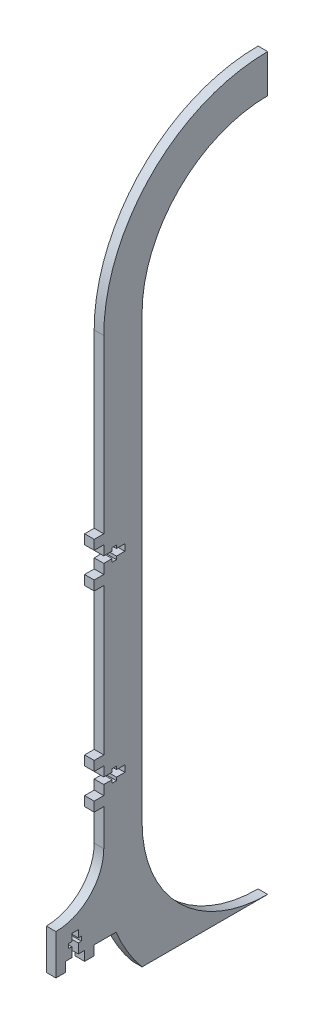
SolidWorks part; units mm, degrees
ref_plane "Front Plane" through (0, 0, 0) normal (0, 0, 1) x (1, 0, 0)
ref_plane "Top Plane" through (0, 0, 0) normal (0, 1, 0) x (1, 0, 0)
ref_plane "Right Plane" through (0, 0, 0) normal (1, 0, 0) x (0, 0, -1)
sketch "Elevator Ball Support Rail" plane through (0, 0, 0) normal (1, 0, 0) x (0, 0, -1)
  line L0 (83.312, 229.362) -> (83.312, 254.762)
  line L1 (-31.75, -124.587) -> (-25.4, -124.587)
  line L2 (83.312, -229.362) -> (0, -229.362)
  line L3 (-31.75, -200.787) -> (-17.2645, -200.787)
  line L4 (-38.1, -207.137) -> (-31.75, -207.137)
  line L5 (-38.1, -200.787) -> (-38.1, -207.137)
  line L6 (0, 146.05) -> (0, -146.05)
  line L7 (-25.4, -148.717) -> (-25.4, -200.787) construction
  line L8 (0, -146.05) -> (0, -229.362) construction
  line L9 (-31.75, -200.787) -> (-31.75, -207.137)
  line L10 (-50.8, -200.787) -> (-46.609, -200.787)
  line L11 (-25.4, 25.781) -> (-25.4, 19.431)
  line L12 (-57.15, -180.467) -> (-57.15, -207.137)
  line L13 (-57.15, -207.137) -> (-50.8, -207.137)
  line L14 (-42.291, -200.787) -> (-38.1, -200.787)
  line L15 (-50.8, -207.137) -> (-50.8, -200.787)
  line L16 (-42.291, -194.437) -> (-42.291, -200.787)
  line L17 (-42.291, -194.437) -> (-40.25, -194.437)
  line L18 (-40.25, -194.437) -> (-40.25, -191.537)
  line L19 (-42.291, -191.537) -> (-42.291, -186.817)
  line L20 (-42.291, -186.817) -> (-46.609, -186.817)
  line L21 (-40.25, -191.537) -> (-42.291, -191.537)
  line L22 (-48.65, -191.537) -> (-48.65, -194.437)
  line L23 (-48.65, -194.437) -> (-46.609, -194.437)
  line L24 (-46.609, -194.437) -> (-46.609, -200.787)
  line L25 (-46.609, -186.817) -> (-46.609, -191.537)
  line L26 (-46.609, -191.537) -> (-48.65, -191.537)
  line L27 (0, -200.787) -> (101.6, -200.787) construction
  line L28 (-31.75, 32.131) -> (-31.75, 25.781)
  line L29 (-31.75, 25.781) -> (-25.4, 25.781)
  line L30 (-25.4, 19.431) -> (-19.865, 19.431)
  line L31 (-19.865, 19.431) -> (-19.865, 21.472)
  line L32 (-19.865, 21.472) -> (-16.965, 21.472)
  line L33 (-16.965, 21.472) -> (-16.965, 19.431)
  line L34 (-16.965, 19.431) -> (-11.43, 19.431)
  line L35 (-11.43, 19.431) -> (-11.43, 15.113)
  line L36 (-11.43, 15.113) -> (-16.965, 15.113)
  line L37 (-16.965, 15.113) -> (-16.965, 13.072)
  line L38 (-16.965, 13.072) -> (-19.865, 13.072)
  line L39 (-19.865, 13.072) -> (-19.865, 15.113)
  line L40 (-19.865, 15.113) -> (-25.4, 15.113)
  line L41 (-25.4, 15.113) -> (-25.4, 8.763)
  line L42 (0, 0) -> (-25.4, 0) construction
  line L43 (-25.4, 8.763) -> (-31.75, 8.763)
  line L44 (-31.75, 8.763) -> (-31.75, 2.413)
  line L45 (-31.75, 2.413) -> (-25.4, 2.413)
  line L46 (-25.4, 2.413) -> (-25.4, -94.869)
  line L47 (-25.4, -94.869) -> (-31.75, -94.869)
  line L48 (-25.4, -101.219) -> (-25.4, -107.569)
  line L49 (-31.75, -94.869) -> (-31.75, -101.219)
  line L50 (-31.75, -101.219) -> (-25.4, -101.219)
  line L51 (-25.4, -107.569) -> (-19.865, -107.569)
  line L52 (-19.865, -107.569) -> (-19.865, -105.528)
  line L53 (-19.865, -105.528) -> (-16.965, -105.528)
  line L54 (-16.965, -105.528) -> (-16.965, -107.569)
  line L55 (-16.965, -107.569) -> (-11.43, -107.569)
  line L56 (-11.43, -107.569) -> (-11.43, -111.887)
  line L57 (-11.43, -111.887) -> (-16.965, -111.887)
  line L58 (-16.965, -111.887) -> (-16.965, -113.928)
  line L59 (-16.965, -113.928) -> (-19.865, -113.928)
  line L60 (-19.865, -113.928) -> (-19.865, -111.887)
  line L61 (-19.865, -111.887) -> (-25.4, -111.887)
  line L62 (-25.4, -111.887) -> (-25.4, -118.237)
  line L63 (-25.4, -118.237) -> (-31.75, -118.237)
  line L64 (-31.75, -118.237) -> (-31.75, -124.587)
  line L65 (-25.4, -148.717) -> (-25.4, -142.367)
  line L66 (-25.4, -124.587) -> (-25.4, -142.367)
  line L67 (-31.75, 32.131) -> (-25.4, 32.131)
  line L68 (-25.4, 32.131) -> (-25.4, 146.05)
  arc A0 (0, 146.05) -> (83.312, 229.362) centre (83.312, 146.05) cw
  arc A1 (83.312, 254.762) -> (-25.4, 146.05) centre (83.312, 146.05) ccw
  arc A2 (0, -146.05) -> (83.312, -229.362) centre (83.312, -146.05) ccw
  arc A3 (-17.2645, -200.787) -> (0, -229.362) centre (83.312, -159.5235) ccw
  arc A4 (-57.15, -180.467) -> (-25.4, -148.717) centre (-57.15, -148.717) ccw
  point P4 (0, 0)
  dimension "D5" = 25.4
  dimension "D4" = 83.312
  dimension "D7" = 83.312
  dimension "D8" = 6.35
  dimension "D14" = 12.7
  dimension "D13" = 6.35
  dimension "D6" = 6.35
  dimension "D3" = 292.1
  dimension "D9" = 22.225
  dimension "D10" = 6.35
  dimension "D11" = 6.35
  dimension "D12" = 6.35
  dimension "D15" = 2.9
  dimension "D16" = 8.4
  dimension "D17" = 6.35
  dimension "D18" = 4.318
  dimension "D19" = 13.97
  dimension "D20" = 54.737
  dimension "D21" = 6.35
  dimension "D22" = 6.35
  dimension "D23" = 4.318
  dimension "D24" = 2.9
  dimension "D25" = 8.4
  dimension "D26" = 6.35
  dimension "D27" = 13.97
  dimension "D28" = 6.35
  dimension "D29" = 4.318
  dimension "D30" = 2.9
  dimension "D31" = 13.97
  dimension "D32" = 6.35
  dimension "D33" = 8.4
  dimension "D34" = 6.35
  dimension "D35" = 6.35
  dimension "D36" = 25.4
  dimension "D37" = 76.2
  dimension "D38" = 203.2
extrude "Boss-Extrude2" add sketch "Elevator Ball Support Rail" along normal blind 6.35 contours A4 L12 L13 L15 L10 L24 L23 L22 L26 L25 L20 L19 L21 L18 L17 L16 L14 L5 L4 L9 L3 A3 L2 A2 L6 A0 L0 A1 L28 L29 L11 L30 L31 L32 L33 L34 L35 L36 L37 L38 L39 L40 L41 L43 L44 L45 L46 L47 L49 L50 region at (0, 1.1865, 2.4978)
equation "\"Ball Diameter\"= 1.75in"
equation "\"Pulley Diameter\" = 1in"
equation "\"Reactor Height\" = 14in"
equation "\"Sheet Thickness\"= 0.25in"
equation "\"Screw Diameter\"= .17in"
equation "\"Robot Diameter\"= 14in"
equation "\"Castor Screw Diameter\"= 0.22in"
equation "\"Wheel Diameter\" = 4in"
equation "\"Nut Diameter\" = 8.4mm"
equation "\"Nut Height\" = 2.9mm"
equation "\"Screw Height\" = 0.55in"
equation "\"D11@Elevator Ball Support Rail\"=\"Sheet Thickness\""
equation "\"Elevator Height\" = 11.5in"
equation "\"D12@Elevator Ball Support Rail\"=\"Sheet Thickness\""
equation "\"D7@Elevator Ball Support Rail\"=\"Elevator Clearance from Axis\""
equation "\"D10@Elevator Ball Support Rail\"=\"Sheet Thickness\""
equation "\"D13@Elevator Ball Support Rail\"=\"Sheet Thickness\""
equation "\"D1@T-Slot\" = \"Screw Diameter\""
equation "\"D16@Elevator Ball Support Rail\"=\"Nut Diameter\""
equation "\"D15@Elevator Ball Support Rail\"=\"Nut Height\""
equation "\"D16@Elevator Ball Support Rail\" = \"Nut Diameter\""
equation "\"D9@Elevator Ball Support Rail\"=\"Ball Diameter\"/2"
equation "\"D1@Boss-Extrude2\"=\"Sheet Thickness\""
equation "\"D18@Elevator Ball Support Rail\"=\"Screw Diameter\""
equation "\"D19@Elevator Ball Support Rail\"=\"Screw Height\""
equation "\"D3@Elevator Ball Support Rail\"=\"Elevator Height\""
equation "\"Elevator Width\" = \"Ball Diameter\" + 0.25in"
equation "\"Elevator Bearing Diameter\" = sqr(2*(\"Sheet Thickness\"^2)) + 0.2in"
equation "\"Elevator Axle Endcap Diameter\" = \"Pulley Diameter\" + 0.25in"
equation "\"Elevator Axle Length\" = \"Elevator Width\" + 8*\"Sheet Thickness\""
equation "\"Elevator Clearance from Axis\" = 3.28in"
equation "\"D4@Elevator Ball Support Rail\"=\"Elevator Clearance from Axis\""
equation "\"D21@Elevator Ball Support Rail\"=\"Sheet Thickness\""
equation "\"D22@Elevator Ball Support Rail\"=\"Sheet Thickness\""
equation "\"D23@Elevator Ball Support Rail\"=\"Screw Diameter\""
equation "\"D24@Elevator Ball Support Rail\"=\"Nut Height\""
equation "\"D25@Elevator Ball Support Rail\"=\"Nut Diameter\""
equation "\"D26@Elevator Ball Support Rail\"=\"Sheet Thickness\""
equation "\"D27@Elevator Ball Support Rail\"=\"Screw Height\""
equation "\"D32@Elevator Ball Support Rail\"=\"Sheet Thickness\""
equation "\"D33@Elevator Ball Support Rail\"=\"Nut Diameter\""
equation "\"D34@Elevator Ball Support Rail\"=\"Sheet Thickness\""
equation "\"D35@Elevator Ball Support Rail\"=\"Sheet Thickness\""
equation "\"D30@Elevator Ball Support Rail\"=\"Nut Height\""
equation "\"D28@Elevator Ball Support Rail\"=\"Sheet Thickness\""
equation "\"D29@Elevator Ball Support Rail\"=\"Screw Diameter\""
equation "\"D31@Elevator Ball Support Rail\"=\"Screw Height\""
